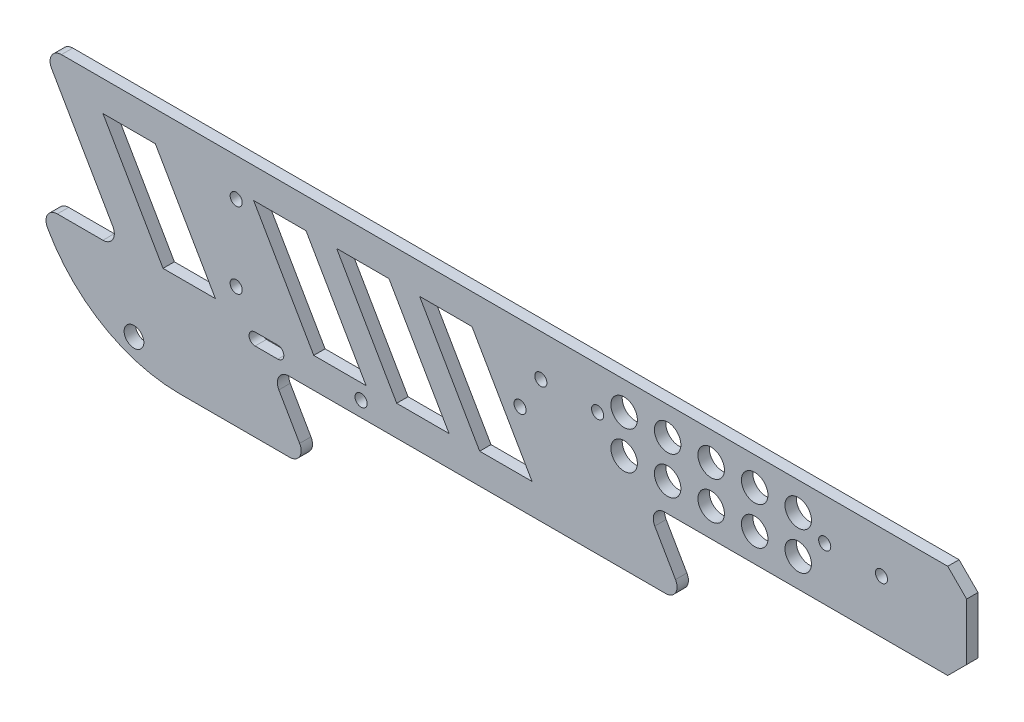
SolidWorks part; units mm, degrees
material "Thornel Mat VMA"
ref_plane "前视基准面" through (0, 0, 0) normal (0, 0, 1) x (1, 0, 0)
ref_plane "上视基准面" through (0, 0, 0) normal (0, 1, 0) x (1, 0, 0)
ref_plane "右视基准面" through (0, 0, 0) normal (1, 0, 0) x (0, 0, -1)
sketch "草图1" plane through (0, 0, 0) normal (0, 0, 1) x (1, 0, 0)
  line L0 (-220, 0) -> (-220, -62) construction
  line L1 (0, 0) -> (-245, 0)
  line L2 (0, 0) -> (0, -62)
  line L3 (0, -62) -> (-245, -62)
  line L4 (-245, 0) -> (-245, -62)
  line L5 (-105, 0) -> (-105, -62) construction
  line L6 (-30, 0) -> (-30, -62) construction
  line L7 (-112.5, -11) -> (-97.5, -11) construction
  line L8 (-37.5, -11) -> (-22.5, -11) construction
  circle A0 centre (-112.5, -11) radius 1.6
  circle A1 centre (-37.5, -11) radius 1.6
  circle A2 centre (-97.5, -11) radius 1.6
  circle A3 centre (-22.5, -11) radius 1.6
  circle A4 centre (-220, -55) radius 2.6
  dimension "D3" = 15
  dimension "D4" = 3.2
  dimension "D5" = 3.2
  dimension "D7" = 11
  dimension "D10" = 5.2
  dimension "D11" = 55
  dimension "D8" = 7
  dimension "D1" = 115
  dimension "D2" = 75
  dimension "D6" = 30
  dimension "D9" = 25
extrude "凸台-拉伸1" add sketch "草图1" along normal mid plane 3
sketch "草图2" plane through (0, 0, 1.5) normal (0, 0, 1) x (1, 0, 0)
  line L0 (0, 0) -> (-245, 0) construction
  circle A0 centre (-193, -10) radius 1.6
  circle A1 centre (-193, -30) radius 1.6
  circle A2 centre (-118, -20) radius 1.6
  circle A3 centre (-220, -55) radius 2.6 construction
  dimension "D1" = 3.2
  dimension "D2" = 10
  dimension "D3" = 20
  dimension "D4" = 27
  dimension "D5" = 75
  dimension "D6" = 20
extrude "切除-拉伸1" cut sketch "草图2" against normal through all
sketch "草图3" plane through (0, 0, 1.5) normal (0, 0, 1) x (1, 0, 0)
  line L0 (0, 0) -> (-244.362, 0)
  line L1 (0, 0) -> (-245, 0) construction
  line L2 (-244.362, 0) -> (-223, -37)
  line L3 (-223, -37) -> (-245, -37)
  line L4 (-245, 0) -> (-245, -62) construction
  line L5 (-245, -37) -> (-245, -62)
  line L6 (-245, -62) -> (-173.638, -62)
  line L7 (-245, -62) -> (0, -62) construction
  line L8 (-173.638, -62) -> (-184.319, -43.5)
  line L9 (-85, -25) -> (0, -25)
  line L10 (0, -62) -> (0, 0) construction
  line L11 (0, -25) -> (0, 0)
  line L12 (-184.319, -43.5) -> (-74.319, -43.5)
  line L13 (-74.319, -43.5) -> (-85, -25)
  circle A1 centre (-193, -10) radius 1.6 construction
  dimension "D2" = 85
  dimension "D3" = 110
  dimension "D1" = 25
  dimension "D4" = 25
  dimension "D5" = 60
  dimension "D6" = 30
extrude "切除-拉伸2" cut sketch "草图3" against normal blind 3 flip side to cut
fillet "圆角1" radius 40 1 edges at (-245, -62, 0)
fillet "圆角2" radius 3 7 edges at (-245, -37, 0) (-244.362, 0, 0) (-223, -37, 0) (-85, -25, 0) (-74.319, -43.5, 0) (-184.319, -43.5, 0) (-173.638, -62, 0)
chamfer "倒角1" distance 5 angle 45 2 edges at (0, -25, 0) (0, 0, 0)
sketch "草图4" plane through (0, 0, 1.5) normal (0, 0, 1) x (1, 0, 0)
  line L0 (-174.5433, -8) -> (-188.3812, -8)
  line L1 (-174.5433, -8) -> (-158.6662, -35.5)
  line L2 (-188.3812, -8) -> (-172.5041, -35.5)
  line L3 (-158.6662, -35.5) -> (-172.5041, -35.5)
  line L4 (-152.6225, -8) -> (-166.4604, -8)
  line L5 (-152.6225, -8) -> (-136.7454, -35.5)
  line L6 (-136.7454, -35.5) -> (-150.5833, -35.5)
  line L7 (-166.4604, -8) -> (-150.5833, -35.5)
  line L8 (-130.7017, -8) -> (-144.5396, -8)
  line L9 (-130.7017, -8) -> (-114.8246, -35.5)
  line L10 (-114.8246, -35.5) -> (-128.6625, -35.5)
  line L11 (-144.5396, -8) -> (-128.6625, -35.5)
  line L13 (-214.3583, -8) -> (-228.1962, -8)
  line L14 (-214.3583, -8) -> (-198.4811, -35.5)
  line L15 (-198.4811, -35.5) -> (-212.319, -35.5)
  line L16 (-241.7639, -4.5) -> (-225.5981, -32.5) construction
  line L17 (-5, 0) -> (-239.1658, 0) construction
  line L18 (-179.1229, -43.5) -> (-79.5152, -43.5) construction
  line L19 (-79.8038, -25) -> (-5, -25) construction
  line L20 (-228.1962, -8) -> (-212.319, -35.5)
  line L21 (-241.7639, -4.5) -> (-225.5981, -32.5) construction
  circle A1 centre (-90.5, -7.5) radius 3.5
  circle A2 centre (-79, -7.5) radius 3.5
  circle A3 centre (-67.5, -7.5) radius 3.5
  circle A4 centre (-56, -7.5) radius 3.5
  circle A5 centre (-44.5, -7.5) radius 3.5
  circle A6 centre (-79, -17.5) radius 3.5
  circle A7 centre (-67.5, -17.5) radius 3.5
  circle A8 centre (-56, -17.5) radius 3.5
  circle A9 centre (-44.5, -17.5) radius 3.5
  circle A10 centre (-90.5, -17.5) radius 3.5
  circle A11 centre (-97.5, -11) radius 1.6 construction
  circle A12 centre (-193, -10) radius 1.6 construction
  circle A13 centre (-118, -20) radius 1.6 construction
  dimension "D7" = 5
  dimension "D11" = 7
  dimension "D12" = 11.5
  dimension "D13" = 10
  dimension "D14" = 7
  dimension "D2" = 5
  dimension "D3" = 8
  dimension "D4" = 8
  dimension "D5" = 5
  dimension "D6" = 7
  dimension "D8" = 2
  dimension "D9" = 7.5
  dimension "D10" = 7.5
  dimension "D16" = 10
  dimension "D1" = 3
  dimension "D15" = 2
extrude "切除-拉伸3" cut sketch "草图4" against normal through all
sketch "草图5" plane through (0, 0, 1.5) normal (0, 0, 1) x (1, 0, 0)
  line L0 (-172.5041, -35.5) -> (-172.5041, -43.5) construction
  line L2 (-179.1229, -43.5) -> (-79.5152, -43.5) construction
  line L3 (-172.5041, -39.5) -> (-185.0041, -39.5) construction
  line L4 (-172.5041, -39.5) -> (-160.0041, -39.5) construction
  line L5 (-188.0041, -39.5) -> (-182.0041, -39.5) construction
  line L6 (-188.0041, -37.9) -> (-182.0041, -37.9)
  line L7 (-188.0041, -41.1) -> (-182.0041, -41.1)
  circle A0 centre (-160.0041, -39.5) radius 1.6
  arc A1 (-188.0041, -37.9) -> (-188.0041, -41.1) centre (-188.0041, -39.5) ccw
  arc A2 (-182.0041, -41.1) -> (-182.0041, -37.9) centre (-182.0041, -39.5) ccw
  point P11 (-102.3246, -39.5)
  point P12 (-185.0041, -39.5)
  dimension "D2" = 12.5
  dimension "D3" = 3.2
  dimension "D1" = 12.5
extrude "切除-拉伸4" cut sketch "草图5" against normal up to next
